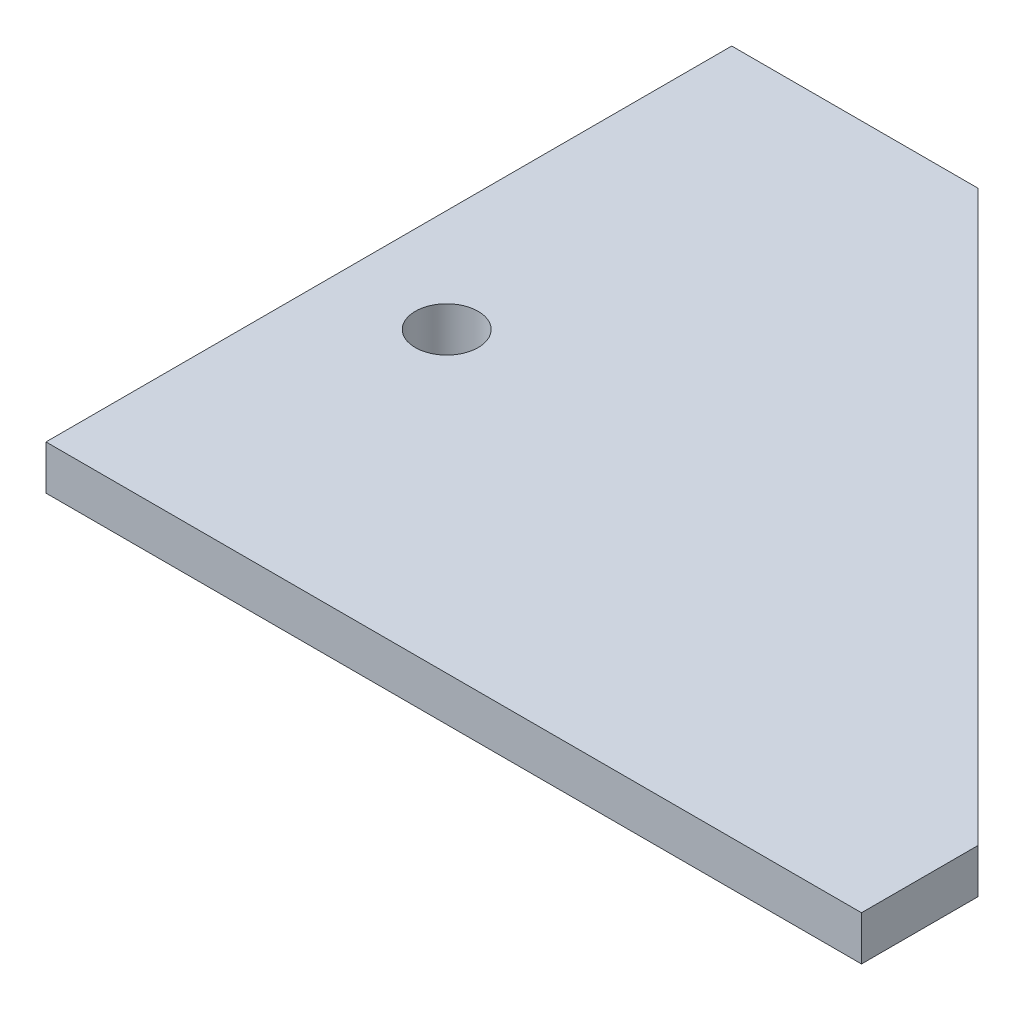
SolidWorks part; units mm, degrees
ref_plane "Front Plane" through (0, 0, 0) normal (0, 0, 1) x (1, 0, 0)
ref_plane "Top Plane" through (0, 0, 0) normal (0, 1, 0) x (1, 0, 0)
ref_plane "Right Plane" through (0, 0, 0) normal (1, 0, 0) x (0, 0, -1)
sketch "Sketch1" plane through (0, 0, 0) normal (0, 1, 0) x (1, 0, 0)
  line L0 (-138.61, 294.305) -> (350, -194.305)
  line L1 (-350, 294.305) -> (-138.61, 294.305)
  line L2 (-350, 294.305) -> (-350, -294.305)
  line L3 (-350, -294.305) -> (350, -294.305)
  line L4 (350, -194.305) -> (350, -294.305)
  line L5 (-350, 294.305) -> (350, -294.305) construction
  point P0 (0, 0)
  dimension "D1" = 588.61
  dimension "D2" = 700
  dimension "D3" = 100
  dimension "D4" = 45
extrude "Boss-Extrude1" add sketch "Sketch1" along normal blind 38.1
sketch "Sketch2" plane through (0, 0, 0) normal (0, -1, 0) x (-1, 0, 0)
  circle A2 centre (261.6329, -38.7118) radius 25 construction
  circle A3 centre (261.6329, -38.7118) radius 25 construction
  circle A4 centre (261.6329, -38.7118) radius 27
  dimension "D1" = 2
extrude "Cut-Extrude1" cut sketch "Sketch2" against normal through all
